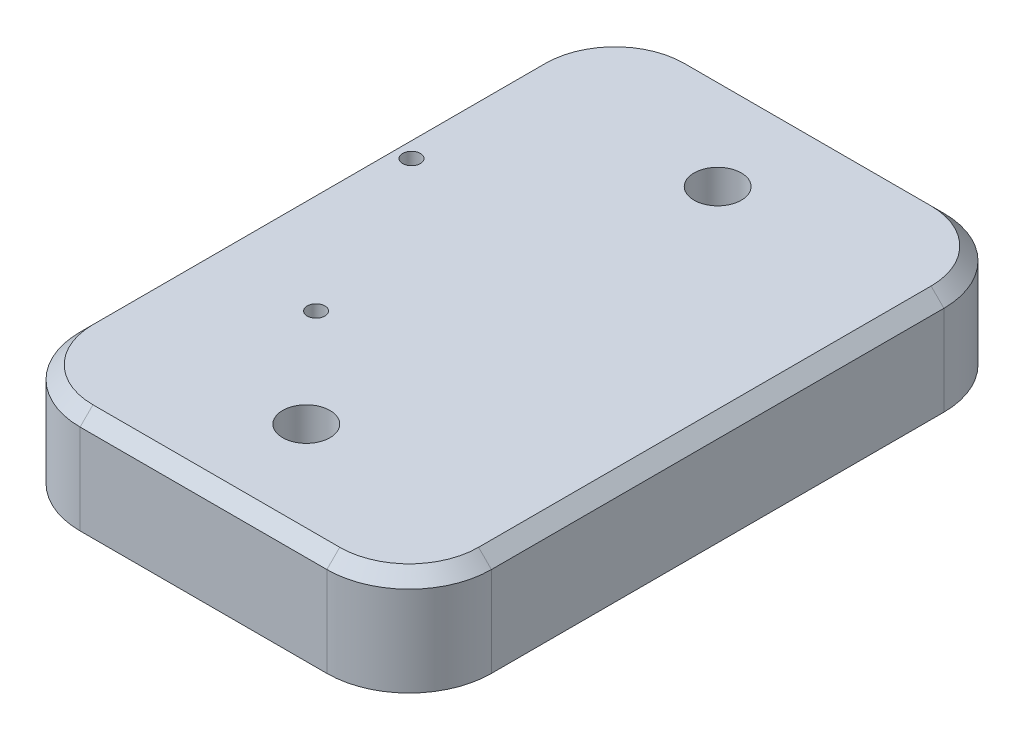
SolidWorks part; units mm, degrees
ref_plane "Front Plane" through (0, 0, 0) normal (0, 0, 1) x (1, 0, 0)
ref_plane "Top Plane" through (0, 0, 0) normal (0, 1, 0) x (1, 0, 0)
ref_plane "Right Plane" through (0, 0, 0) normal (1, 0, 0) x (0, 0, -1)
sketch "Sketch1" plane through (0, 0, 0) normal (1, 0, 0) x (0, 0, -1)
  line L3 (0, 12.7) -> (76.2, 12.7)
  line L4 (76.2, 12.7) -> (76.2, 0)
  line L5 (76.2, 0) -> (0, 0)
  line L6 (0, 12.7) -> (0, 0)
  dimension "D1" = 12.7
  dimension "D3" = 76.2
extrude "Boss-Extrude1" add sketch "Sketch1" along normal blind 50.8
sketch "Sketch3" plane through (0, 0, 0) normal (0, -1, 0) x (1, 0, 0)
  line L0 (50.8, 0) -> (0, 0) construction
  line L1 (25.4, -76.2) -> (25.4, 0) construction
  line L2 (50.8, -76.2) -> (0, -76.2) construction
  line L3 (0, 0) -> (0, -76.2) construction
  line L5 (50.8, -76.2) -> (0, -76.2) construction
  circle A1 centre (13.9065, -25.4) radius 1.0922
  circle A2 centre (3.4925, -47.5996) radius 1.0922
  circle A3 centre (25.4, -63.5) radius 2.921
  circle A4 centre (25.4, -12.7) radius 2.921
  dimension "D1" = 2.1844
  dimension "D6" = 5.842
  dimension "D2" = 10.414
  dimension "D3" = 22.1996
  dimension "D4" = 25.4
  dimension "D5" = 3.4925
  dimension "D7" = 50.8
  dimension "D8" = 12.7
extrude "Cut-Extrude2" cut sketch "Sketch3" against normal through all
fillet "Fillet1" radius 10.16 4 edges at (0, 6.35, 0) (50.8, 6.35, 0) (0, 6.35, -76.2) (50.8, 6.35, -76.2)
chamfer "Chamfer1" distance 1.5875 angle 45 8 edges at (0, 12.7, -38.1) (2.9758, 12.7, -2.9758) (25.4, 12.7, 0) (47.8242, 12.7, -2.9758) (50.8, 12.7, -38.1) (47.8242, 12.7, -73.2242) (25.4, 12.7, -76.2) (2.9758, 12.7, -73.2242)
